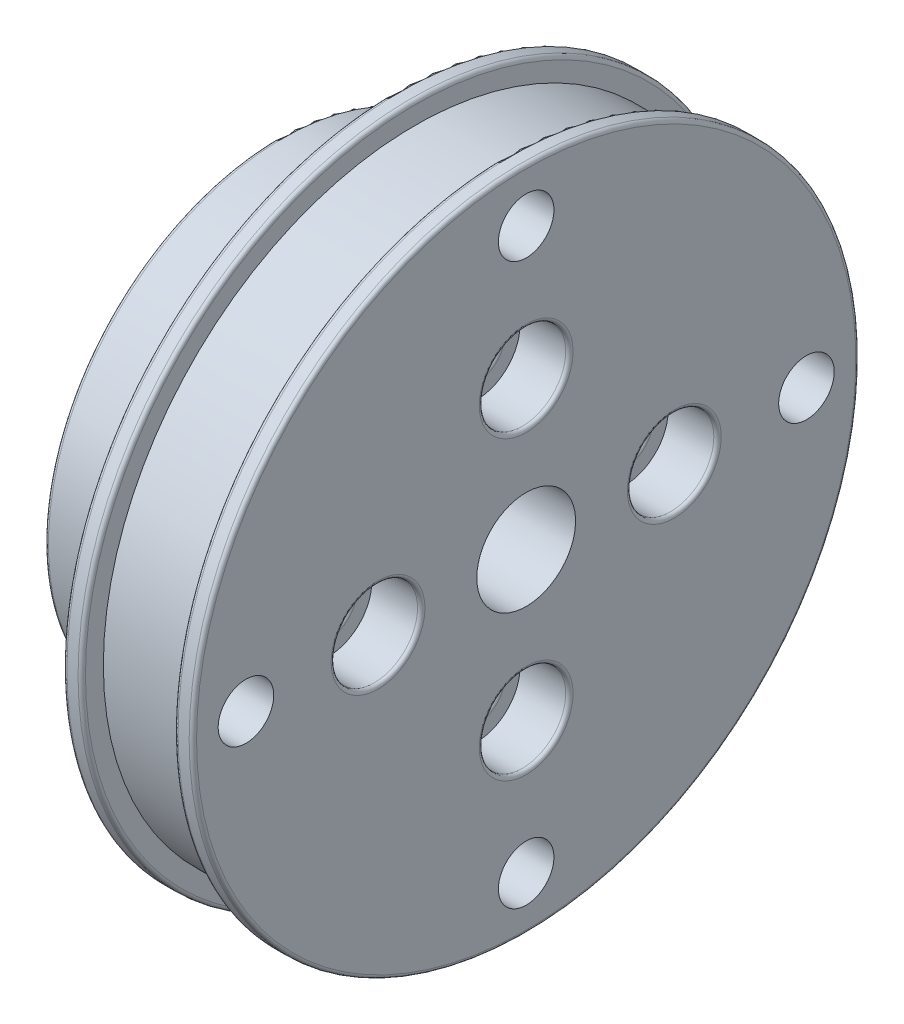
SolidWorks part; units mm, degrees
ref_plane "Front Plane" through (0, 0, 0) normal (0, 0, 1) x (1, 0, 0)
ref_plane "Top Plane" through (0, 0, 0) normal (0, 1, 0) x (1, 0, 0)
ref_plane "Right Plane" through (0, 0, 0) normal (1, 0, 0) x (0, 0, -1)
sketch "Sketch1" plane through (0, 0, 0) normal (0, 1, 0) x (1, 0, 0)
  line L0 (0, 0) -> (5.179, 0) construction
  line L1 (0, 0) -> (0, 4) construction
  line L2 (0, 19) -> (0, 27)
  line L3 (0, 27) -> (1.5, 27)
  line L4 (1.5, 27) -> (1.5, 25.25)
  line L5 (1.5, 25.25) -> (9, 25.25)
  line L6 (9, 25.25) -> (9, 27)
  line L7 (9, 27) -> (10.5, 27)
  line L8 (10.5, 27) -> (10.5, 17.5)
  line L12 (10.5, 17.5) -> (10.5, 4)
  line L16 (0, 19) -> (-9.5, 19)
  line L17 (-9.5, 4) -> (-9.5, 19)
  line L18 (-9.5, 4) -> (10.5, 4)
  dimension "D1" = 23
  dimension "D2" = 10.5
  dimension "54/2" = 27
  dimension "D3" = 25.25
  dimension "D4" = 9.5
  dimension "D5" = 15
  dimension "D6" = 7.5
revolve "Revolve1" add sketch "Sketch1" angle 360 about L0
fillet "Fillet1" radius 0.3 4 edges at (0, 0, 27) (1.5, 0, 27) (9, 0, 27) (10.5, 0, 27)
sketch "Sketch2" plane through (10.5, 0, 0) normal (1, 0, 0) x (0, 0, -1)
  circle A0 centre (0, 0) radius 12
  circle A1 centre (-12, 0) radius 2
  circle A2 centre (-12, 0) radius 3.5
  circle A3 centre (0, 12) radius 3.5
  circle A4 centre (0, 12) radius 2
  circle A5 centre (12, 0) radius 3.5
  circle A6 centre (12, 0) radius 2
  circle A7 centre (0, -12) radius 3.5
  circle A8 centre (0, -12) radius 2
  point P18 (0, 0)
  dimension "D1" = 24
  dimension "D2" = 4
  dimension "D3" = 7
  dimension "D4" = 4
extrude "Cut-Extrude1" cut sketch "Sketch2" against normal through all contours A1 | A4 | A6 | A8
extrude "Cut-Extrude2" cut sketch "Sketch2<3>" against normal blind 4 contours A2 | A7 | A5 | A3
sketch "Sketch2<3>" plane through (10.5, 0, 0) normal (1, 0, 0) x (0, 0, -1) same geometry as "Sketch2"
fillet "Fillet2" radius 0.3 15 edges at (6.5, -12, -2) (10.5, -12, -3.5) (6.5, 0, -14) (10.5, 0, -15.5) (6.5, 0, 10) (10.5, 0, 8.5) (6.5, 12, -2) (10.5, 12, -3.5) (0, 0, 19) (-9.5, 0, 19) (-9.5, 0, 4) (-9.5, -12, -2) (-9.5, 0, -14) (-9.5, 12, -2) (-9.5, 0, 10)
sketch "Sketch3" plane through (0, 0, 0) normal (-1, 0, 0) x (0, 0, 1)
  line L0 (0, 26.7) -> (0, 18.7) construction
  circle A0 centre (0, 0) radius 26.7 construction
  circle A1 centre (0, 0) radius 18.7 construction
  circle A2 centre (0, 22.7) radius 2.25
  circle A3 centre (22.7, 0) radius 2.25
  circle A4 centre (0, -22.7) radius 2.25
  circle A5 centre (-22.7, 0) radius 2.25
  circle A6 centre (0, 0) radius 22.7 construction
  point P18 (0, 0)
  dimension "D1" = 4
  dimension "D2" = 45.4
extrude "Cut-Extrude3" cut sketch "Sketch3" against normal through all
